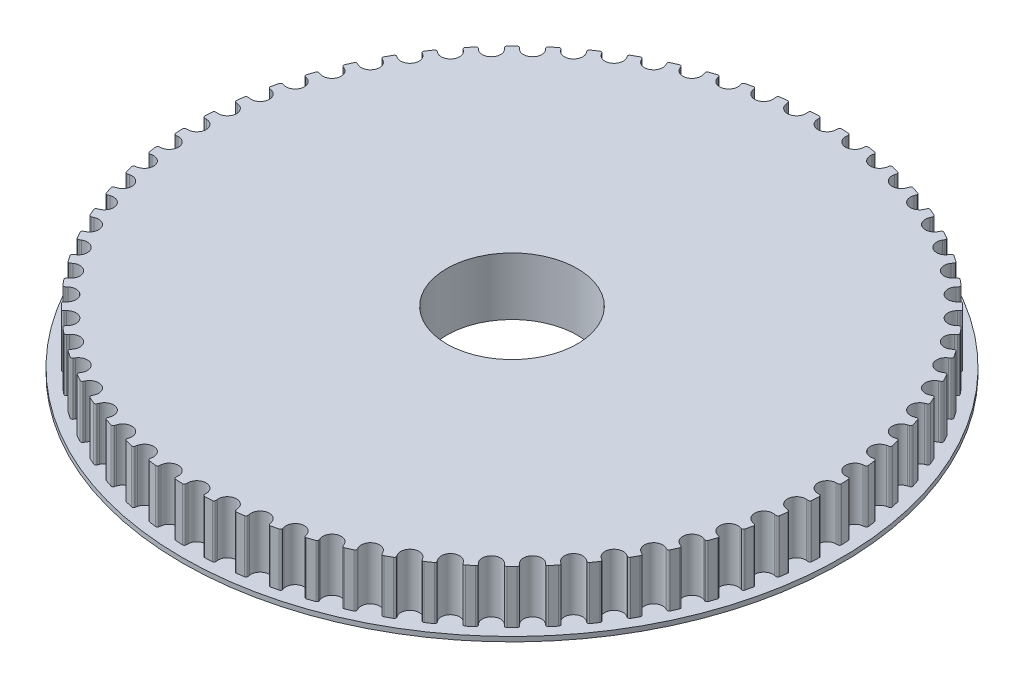
SolidWorks part; units mm, degrees
ref_plane "Front Plane" through (0, 0, 0) normal (0, 0, 1) x (1, 0, 0)
ref_plane "Top Plane" through (0, 0, 0) normal (0, 1, 0) x (1, 0, 0)
ref_plane "Right Plane" through (0, 0, 0) normal (1, 0, 0) x (0, 0, -1)
sketch "Эскиз7" plane through (0, 0, 0) normal (0, 1, 0) x (1, 0, 0)
  circle A0 centre (0, 0) radius 56
  dimension "D1" = 112
extrude "Бобышка-Вытянуть4" add sketch "Эскиз7" along normal blind 0.8
sketch "Эскиз9" plane through (0, 0.8, 0) normal (0, 1, 0) x (1, 0, 0)
  circle A2 centre (0, 0) radius 54.14
  dimension "D1" = 108.28
extrude "Бобышка-Вытянуть6" add sketch "Эскиз9" along normal blind 9 contours A2 region at (0, 0.8, 0)
sketch "Эскиз11" plane through (0, 9.8, 0) normal (0, 1, 0) x (1, 0, 0)
  line L0 (0, 0) -> (-1.7313, 59.395)
  line L1 (0, 0) -> (1.7313, 59.395)
  line L2 (1.7313, 59.395) -> (-1.7313, 59.395)
  circle A0 centre (0, 0) radius 54.14
  circle A1 centre (0, 0) radius 51.98
  circle A2 centre (0, 53.54) radius 1.56
  circle M11 centre (0, 0) radius 54.14
  dimension "D1" = 108.28
  dimension "D2" = 103.96
  dimension "D3" = 3.12
extrude "Вырез-Вытянуть3" cut sketch "Эскиз11" against normal blind 9 contours A2 A0 | A2 L0 M11 | A2 L1 M11 region at (-1.5344, 9.8, -53.9638) region at (0, 9.8, -53.1844) region at (1.5344, 9.8, -53.9638)
fillet "Скругление1" radius 0.305 2 edges at (-1.5775, 5.3, -54.117) (1.5775, 5.3, -54.117)
pattern_circular "Круговой массив1" count 68 over 360 about axis through (0, 0.8, 0) along (0, -1, 0) of "Скругление1", "Вырез-Вытянуть3"
sketch "Эскиз13" plane through (0, 9.8, 0) normal (0, 1, 0) x (1, 0, 0)
  circle A0 centre (0, 0) radius 11.1
  dimension "D1" = 22.2
extrude "Вырез-Вытянуть4" cut sketch "Эскиз13" against normal through all
